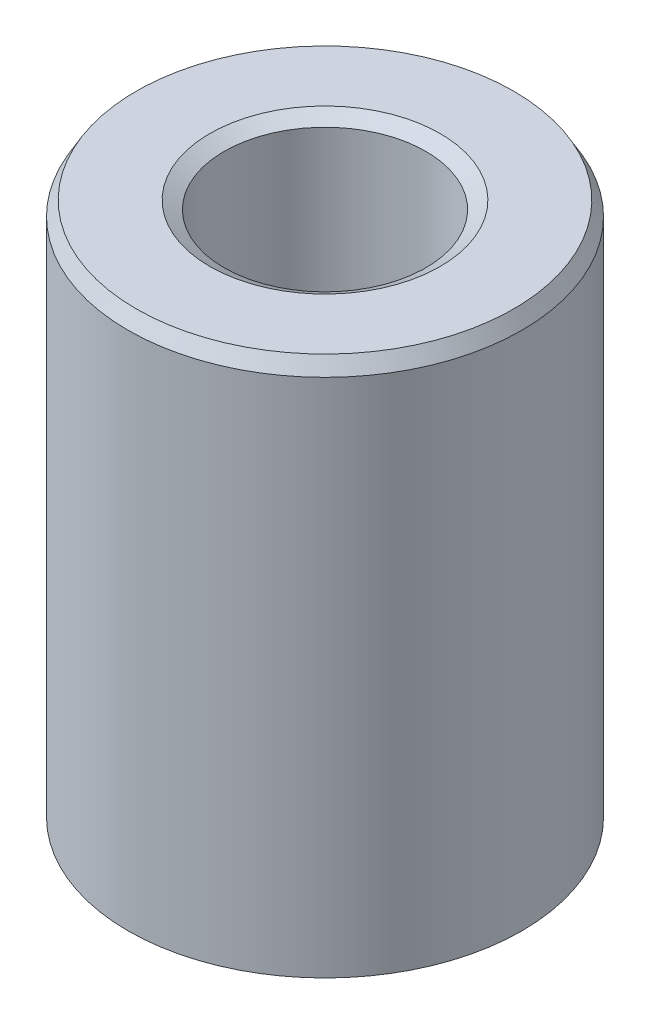
SolidWorks part; units mm, degrees
ref_plane "Front Plane" through (0, 0, 0) normal (0, 0, 1) x (1, 0, 0)
ref_plane "Top Plane" through (0, 0, 0) normal (0, 1, 0) x (1, 0, 0)
ref_plane "Right Plane" through (0, 0, 0) normal (1, 0, 0) x (0, 0, -1)
sketch "Sketch1" plane through (0, 0, 0) normal (0, 1, 0) x (1, 0, 0)
  circle A0 centre (0, 0) radius 40
  dimension "SLEEVE_OD" = 80
extrude "Boss-Extrude1" add sketch "Sketch1" along normal blind 110.2357
sketch "Sketch2" plane through (0, 0, 0) normal (0, 1, 0) x (1, 0, 0)
  circle A0 centre (0, 0) radius 20.486
  dimension "BORE_D" = 40.9721
extrude "Cut-Extrude1" cut sketch "Sketch2" along normal through all
chamfer "Chamfer1" distance 2.909 angle 30 4 edges at (0, 110.2357, 20.486) (0, 0, 20.486) (0, 0, 40) (0, 110.2357, 40) first distance on face at (0, 110.2357, 20.486) first distance on face at (0, 0, 20.486) first distance on face at (0, 110.2357, 40)
